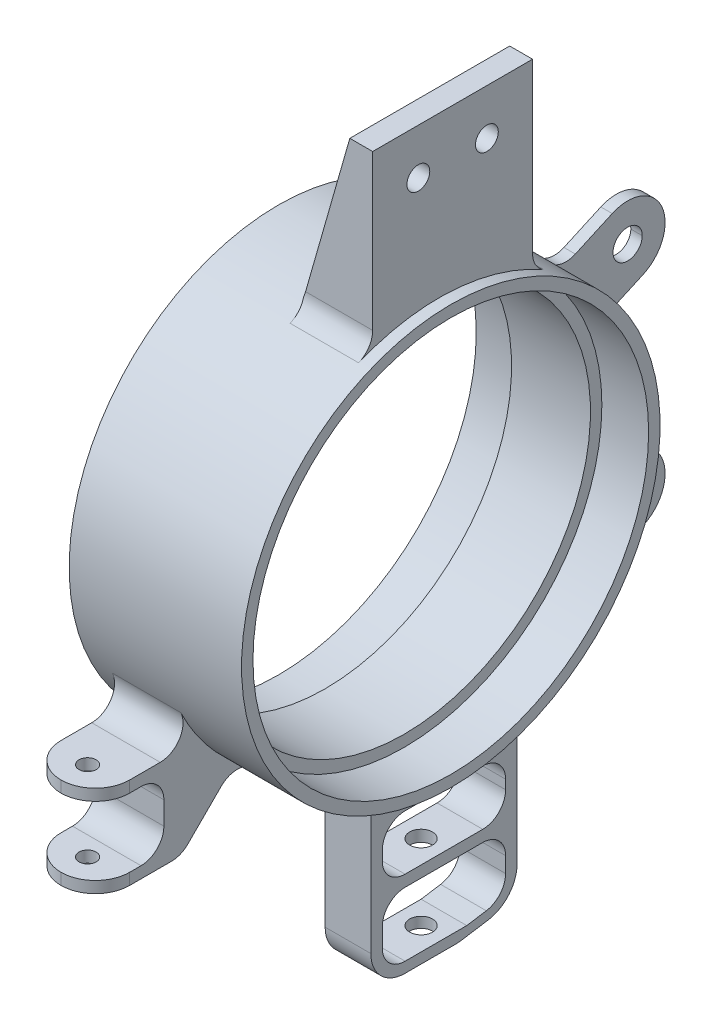
SolidWorks part; units mm, degrees
ref_plane "Front Plane" through (0, 0, 0) normal (0, 0, 1) x (1, 0, 0)
ref_plane "Top Plane" through (0, 0, 0) normal (0, 1, 0) x (1, 0, 0)
ref_plane "Right Plane" through (0, 0, 0) normal (1, 0, 0) x (0, 0, -1)
sketch "Sketch1" plane through (0, 0, 0) normal (0, 0, 1) x (1, 0, 0)
  line L0 (47.925, 0) -> (0, 0) construction
  line L1 (47.925, 55) -> (34.925, 55)
  line L2 (34.925, 55) -> (34.925, 51.825)
  line L3 (34.925, 51.825) -> (13, 51.825)
  line L4 (13, 51.825) -> (13, 55)
  line L5 (13, 55) -> (0, 55)
  line L6 (47.925, 55) -> (47.925, 58.175)
  line L7 (47.925, 58.175) -> (0, 58.175)
  line L8 (0, 58.175) -> (0, 55)
  line L9 (41.425, 55) -> (58.951, 55) construction
  point P11 (6.5, 55)
  point P12 (41.425, 55)
  dimension "D2" = 3.175
  dimension "D3" = 13
  dimension "D4" = 34.925
  dimension "D5" = 3.175
  dimension "D6" = 17.526
  dimension "D7" = 55
revolve "Revolve1" add sketch "Sketch1" angle 360 about L0 reverse direction yes
ref_plane "upper a-arm plane" through (0, 58.175, 0) normal (0, 1, 0) x (1, 0, 0)
ref_plane "rear tierod plane" through (0, 0, 76.2) normal (0, 0, 1) x (1, 0, 0)
sketch "Sketch2" plane through (0, 0, 76.2) normal (0, 0, 1) x (1, 0, 0)
  line L1 (6.254, -34.29) -> (25.304, -34.29)
  line L2 (6.254, -34.29) -> (6.254, -37.465)
  line L3 (6.254, -37.465) -> (25.304, -37.465)
  line L4 (25.304, -34.29) -> (25.304, -37.465)
  point P6 (15.779, -46.99)
  point P10 (15.779, -37.465)
  dimension "D1" = 9.525
  dimension "D2" = 19.05
  dimension "D3" = 3.175
extrude "Boss-Extrude1" add sketch "Sketch2" against normal up to surface (29.205 mm away) up to face at (0, -58.175, 0)
sketch "Sketch4" plane through (0, 58.175, 0) normal (0, 1, 0) x (1, 0, 0)
  line L0 (38.3366, 19.6167) -> (38.3366, -12.1333)
  line L1 (38.3366, -12.1333) -> (25.6366, -12.1333)
  line L2 (25.6366, -12.1333) -> (25.6366, -18.4833)
  line L3 (25.6366, -18.4833) -> (44.6866, -18.4833)
  line L4 (44.6866, -18.4833) -> (44.6866, 25.9667)
  line L5 (44.6866, 25.9667) -> (25.6366, 25.9667)
  line L6 (25.6366, 25.9667) -> (25.6366, 19.6167)
  line L7 (25.6366, 19.6167) -> (38.3366, 19.6167)
  point P2 (19.2866, 3.7417)
  point P11 (38.3366, 3.7417)
  dimension "D1" = 31.75
  dimension "D2" = 6.35
  dimension "D3" = 6.35
  dimension "D4" = 19.05
  dimension "D5" = 12.7
extrude "Boss-Extrude2" add sketch "Sketch4" along normal blind 44.45 and the other way up to surface other way up to face at (15.779, -35.8883, 45.7638)
sketch "Sketch5" plane through (0, 0, 18.4833) normal (0, 0, 1) x (1, 0, 0)
  line L0 (38.3366, 102.625) -> (25.6366, 58.175)
  line L1 (47.925, 58.175) -> (0, 58.175) construction
  line L2 (25.6366, 102.625) -> (25.6366, 55.1607) construction
  line L3 (25.6366, 58.175) -> (25.6366, 102.625)
  line L4 (25.6366, 102.625) -> (38.3366, 102.625)
extrude "Cut-Extrude1" cut sketch "Sketch5" against normal through all both and the other way through all
ref_plane "Plane3" through (0, -58.175, 0) normal (0, -1, 0) x (-1, 0, 0)
sketch "Sketch7" plane through (0, -58.175, 0) normal (0, -1, 0) x (-1, 0, 0)
  line L9 (-32.289, 34.0454) -> (-19.589, 34.0454)
  line L10 (-32.289, 34.0454) -> (-32.289, -6.5946)
  line L11 (-32.289, -6.5946) -> (-19.589, -6.5946)
  line L12 (-19.589, 34.0454) -> (-19.589, -6.5946)
  line L13 (-32.289, 34.0454) -> (-19.589, -6.5946) construction
  line L14 (-32.289, -6.5946) -> (-19.589, 34.0454) construction
  point P0 (-25.939, 13.7254)
  dimension "D1" = 12.7
  dimension "D2" = 40.64
extrude "Boss-Extrude3" add sketch "Sketch7" against normal up to surface and the other way blind 53.975
sketch "Sketch8" plane through (32.289, 0, 0) normal (1, 0, 0) x (0, 0, -1)
  line L0 (34.0454, -112.15) -> (34.0454, -47.1725) construction
  line L13 (13.7254, -101.6) -> (13.7254, -109.22) construction
  line L14 (-3.4196, -109.22) -> (20.0754, -109.22)
  line L15 (-3.4196, -91.44) -> (30.8704, -91.44)
  line L16 (-3.4196, -109.22) -> (-3.4196, -91.44)
  line L17 (13.7254, -109.22) -> (13.7254, -114.7521) construction
  line L18 (-6.5946, -112.15) -> (-6.5946, -57.8) construction
  line L22 (1.0254, -106.68) -> (26.4254, -106.68) construction
  line L24 (30.8704, -91.44) -> (30.8704, -107.5246)
  line L25 (20.0754, -109.22) -> (30.8704, -107.5246)
  line L28 (17.7905, -112.15) -> (34.0454, -109.597)
  line L29 (-3.4196, -73.025) -> (30.8704, -73.025)
  line L30 (-3.4196, -73.025) -> (-3.4196, -88.265)
  line L31 (-3.4196, -88.265) -> (30.8704, -88.265)
  line L32 (30.8704, -73.025) -> (30.8704, -88.265)
  line L33 (-3.4196, -73.025) -> (30.8704, -88.265) construction
  line L34 (-3.4196, -88.265) -> (30.8704, -73.025) construction
  line L35 (34.0454, -112.15) -> (-6.5946, -112.15) construction
  line L36 (34.0454, -109.597) -> (34.0454, -112.15)
  line L37 (34.0454, -112.15) -> (17.7905, -112.15)
  circle A1 centre (0, 0) radius 115.57 construction
  point P7 (13.7254, -109.22)
  point P15 (13.7254, -91.44)
  point P20 (13.7254, -106.68)
  point P24 (13.7254, -80.645)
  dimension "D1" = 6.35
  dimension "D2" = 7.62
  dimension "D3" = 10.16
  dimension "D4" = 2.54
  dimension "D5" = 25.4
  dimension "D6" = 5.08
  dimension "D7" = 3.175
  dimension "D8" = 7.62
  dimension "D9" = 1.524
  dimension "D11" = 3.175
  dimension "D12" = 15.24
extrude "Cut-Extrude4" cut sketch "Sketch8" against normal through all
sketch "Sketch9" plane through (25.304, 0, 0) normal (1, 0, 0) x (0, 0, -1)
  line L0 (-44.5051, -37.465) -> (-57.15, -37.465)
  line L1 (-44.5051, -37.465) -> (-76.2, -37.465) construction
  line L2 (-57.15, -37.465) -> (-57.15, -56.515)
  line L3 (-57.15, -56.515) -> (-76.2, -56.515)
  line L5 (-76.2, -59.69) -> (-52.3617, -59.69)
  line L6 (-52.3617, -59.69) -> (-37.3083, -44.6366)
  line L9 (-76.2, -59.69) -> (-76.2, -56.515)
  line L10 (-76.2, -37.465) -> (-76.2, -34.29) construction
  circle A0 centre (0, 0) radius 58.175 construction
  arc A1 (-44.5051, -37.465) -> (-37.3083, -44.6366) centre (0, 0) ccw
  dimension "D1" = 19.05
  dimension "D2" = 3.175
  dimension "D3" = 19.05
  dimension "D4" = 10.16
  dimension "D5" = 45
sketch "Sketch10" plane through (30.0204, 0, 0) normal (-1, 0, 0) x (0, 0, 1)
  line L0 (-56.4595, -14.0233) -> (-71.344, -20.7317)
  line L1 (-62.786, -39.7203) -> (-47.9014, -33.0119)
  line L2 (-67.065, -30.226) -> (0, 0) construction
  line L3 (0, 0) -> (-67.065, 30.226) construction
  line L4 (-47.9014, 33.0119) -> (-62.786, 39.7203)
  line L5 (-71.344, 20.7317) -> (-56.4595, 14.0233)
  line L6 (-67.065, 30.226) -> (-77.479, 30.226) construction
  line L7 (-67.065, -30.226) -> (-77.479, -30.226) construction
  circle A0 centre (-67.065, -30.226) radius 4.064 construction
  circle A1 centre (-67.065, -30.226) radius 4.064
  circle A2 centre (-67.065, 30.226) radius 4.064 construction
  circle A3 centre (-67.065, 30.226) radius 4.064
  circle A4 centre (0, 0) radius 58.175 construction
  arc A5 (-47.9014, 33.0119) -> (-56.4595, 14.0233) centre (0, 0) ccw
  arc A6 (-71.344, -20.7317) -> (-62.786, -39.7203) centre (-67.065, -30.226) ccw
  arc A7 (-62.786, 39.7203) -> (-71.344, 20.7317) centre (-67.065, 30.226) ccw
  arc A8 (-56.4595, -14.0233) -> (-47.9014, -33.0119) centre (0, 0) ccw
  dimension "D1" = 6.35
  dimension "D2" = 6.35
extrude "Boss-Extrude5" add sketch "Sketch10" along normal blind 3.175
extrude "Boss-Extrude6" add sketch "Sketch9" against normal up to surface (19.05 mm away) up to face at (6.254, -35.8829, 60.9819)
sketch "Sketch6" plane through (0, -34.29, 0) normal (0, 1, 0) x (1, 0, 0)
  circle A0 centre (15.779, -68.8246) radius 2.3813
  dimension "D1" = 4.7625
extrude "Cut-Extrude2" cut sketch "Sketch6" against normal through all both and the other way through all
sketch "Sketch12" plane through (44.6866, 0, 0) normal (1, 0, 0) x (0, 0, -1)
  line L0 (13.2667, 89.925) -> (-5.7833, 89.925) construction
  line L1 (-18.4833, 102.625) -> (25.9667, 102.625) construction
  circle A0 centre (-5.7833, 89.925) radius 3.175
  circle A1 centre (13.2667, 89.925) radius 3.175
  point P6 (3.7417, 102.625)
  point P7 (3.7417, 89.925)
  dimension "D1" = 6.35
  dimension "D2" = 19.05
  dimension "D3" = 12.7
extrude "Cut-Extrude5" cut sketch "Sketch12" against normal through all
fillet "0.25 Fillet5" radius 6.35 21 edges at (25.939, -107.5246, -30.8704) (25.939, -73.025, 3.4196) (25.939, -73.025, -30.8704) (25.939, -88.265, -30.8704) (25.939, -91.44, -30.8704) (25.939, -91.44, 3.4196) (25.939, -88.265, 3.4196) (25.939, -109.22, 3.4196) (35.1616, 55.1607, 18.4833) (35.1616, 52.0583, -25.9667) (28.4329, 14.0233, -56.4595) (28.4329, 33.0119, -47.9014) (28.4329, -14.0233, -56.4595) (28.4329, -33.0119, -47.9014) (15.779, -34.29, 46.995) (15.779, -44.6366, 37.3083) (15.779, -56.515, 57.15) (15.779, -37.465, 57.15) (15.779, -59.69, 52.3617) (31.9866, 56.8956, 12.1333) (31.9866, 54.7678, -19.6167)
sketch "Sketch13" plane through (0, -88.265, 0) normal (0, 1, 0) x (1, 0, 0)
  line L0 (32.289, -3.4196) -> (32.289, 30.8704) construction
  line L1 (32.289, 24.5204) -> (19.589, 24.5204) construction
  circle A0 centre (25.939, 13.7254) radius 3.175
  point P5 (32.289, 13.7254)
  point P8 (25.939, 24.5204)
  dimension "D1" = 6.35
extrude "Cut-Extrude6" cut sketch "Sketch13" against normal through all
fillet "0.375 Fillet6" radius 9.525 9 edges at (25.939, -47.1725, -34.0454) (25.939, -57.8, 6.5946) (25.939, -109.597, -34.0454) (25.939, -112.15, -17.7905) (25.939, -112.15, 6.5946) (25.304, -35.8775, 76.2) (6.254, -35.8775, 76.2) (25.304, -58.1025, 76.2) (6.254, -58.1025, 76.2)
ref_plane "Plane4" through (0, 30.226, 0) normal (0, 1, 0) x (1, 0, 0)
ref_plane "Plane5" through (0, -30.226, 0) normal (0, 1, 0) x (1, 0, 0)
split line "Split Line1"
split line "Split Line2"
